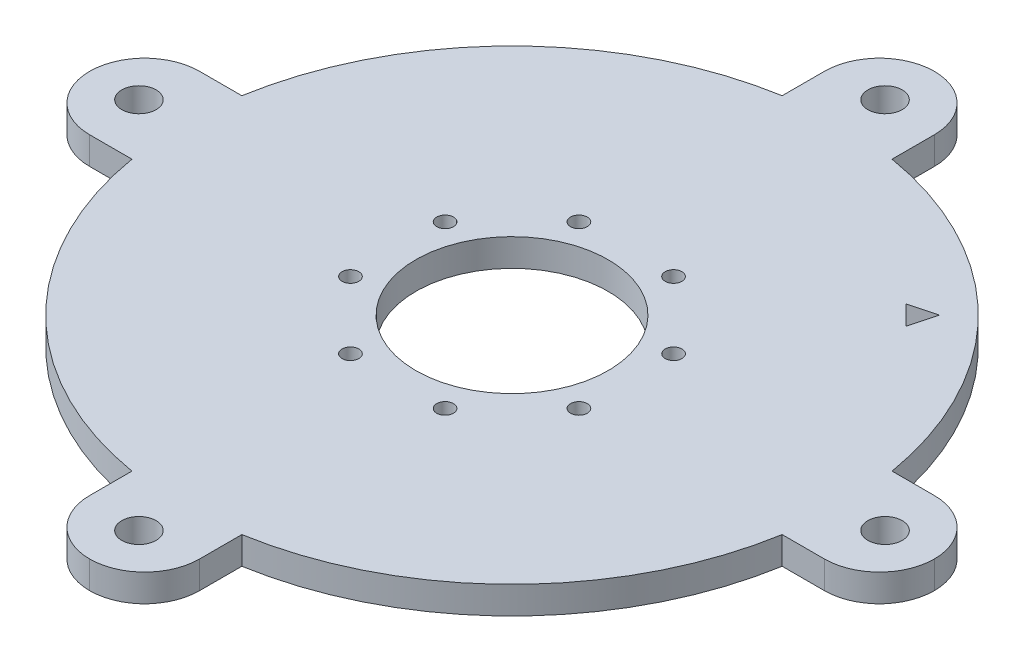
SolidWorks part; units mm, degrees
ref_plane "Front Plane" through (0, 0, 0) normal (0, 0, 1) x (1, 0, 0)
ref_plane "Top Plane" through (0, 0, 0) normal (0, 1, 0) x (1, 0, 0)
ref_plane "Right Plane" through (0, 0, 0) normal (1, 0, 0) x (0, 0, -1)
sketch "Sketch1" plane through (0, 0, 0) normal (0, 1, 0) x (1, 0, 0)
  circle A0 centre (0, 0) radius 155
  dimension "D1" = 310
extrude "Boss-Extrude1" add sketch "Sketch1" along normal blind 10
sketch "Sketch2" plane through (0, 10, 0) normal (0, 1, 0) x (1, 0, 0)
  line L0 (0, 135.7645) -> (135.7645, 0) construction
  line L1 (135.7645, 0) -> (0, -135.7645) construction
  line L2 (0, -135.7645) -> (-135.7645, 0) construction
  line L3 (-135.7645, 0) -> (0, 135.7645) construction
  line L4 (0, 0) -> (67.8823, 67.8823) construction
  line L5 (0, 0) -> (0, 55.7409) construction
  circle A0 centre (-135.7645, 0) radius 6.25
  circle A1 centre (0, -135.7645) radius 6.25
  circle A2 centre (135.7645, 0) radius 6.25
  circle A4 centre (0, 135.7645) radius 6.25
  dimension "D13" = 12.5
  dimension "D15" = 192
  dimension "D17" = 96
  dimension "D14" = 96
  dimension "D16" = 192
  dimension "D18" = 45
extrude "Cut-Extrude1" cut sketch "Sketch2" against normal through all
sketch "Sketch3" plane through (0, 10, 0) normal (0, 1, 0) x (1, 0, 0)
  circle A0 centre (0, 0) radius 35
  dimension "D1" = 70
extrude "Cut-Extrude2" cut sketch "Sketch3" against normal through all
sketch "Sketch4" plane through (0, 10, 0) normal (0, 1, 0) x (1, 0, 0)
  line L0 (0, 0) -> (0, 155) construction
  line L1 (0, 0) -> (59.3159, 143.2013) construction
  circle A0 centre (17.2208, 41.5746) radius 3.05
  circle A3 centre (0, 0) radius 155 construction
  dimension "D2" = 6.1
  dimension "D1" = 22.5
  dimension "D3" = 45
extrude "Cut-Extrude3" cut sketch "Sketch4" against normal through all
pattern_circular "CirPattern1" count 8 every 45 about axis through (0, 0, 0) along (0, 1, 0) of "Cut-Extrude3"
sketch "Sketch5" plane through (0, 10, 0) normal (0, 1, 0) x (1, 0, 0)
  line L0 (0, 0) -> (-155, 0) construction
  line L1 (0, 0) -> (0, 155) construction
  line L2 (-86.2957, 20) -> (-153.7043, 20)
  line L3 (-86.2957, 20) -> (-86.2957, -20)
  line L4 (-86.2957, -20) -> (-153.7043, -20)
  line L5 (-153.7043, 20) -> (-153.7043, -20)
  line L6 (-86.2957, 20) -> (-153.7043, -20) construction
  line L7 (-86.2957, -20) -> (-153.7043, 20) construction
  line L9 (-20, 86.2957) -> (20, 86.2957)
  line L10 (-20, 86.2957) -> (-20, 153.7043)
  line L11 (-20, 153.7043) -> (20, 153.7043)
  line L12 (20, 86.2957) -> (20, 153.7043)
  line L13 (-20, 86.2957) -> (20, 153.7043) construction
  line L14 (-20, 153.7043) -> (20, 86.2957) construction
  circle A0 centre (0, 0) radius 120
  circle A1 centre (0, 0) radius 155 construction
  point P3 (-120, 0)
  point P12 (0, 120)
  circle M30 centre (0, 0) radius 155
  dimension "D1" = 240
  dimension "D2" = 40
  dimension "D3" = 40
extrude "Cut-Extrude4" cut sketch "Sketch5" against normal blind 10 contours A0 L10 L2 M30 | L5 M30 region at (-91.3175, 10, -91.3175) region at (-154.2227, 10, 0)
pattern_circular "CirPattern3" count 4 every 90 about axis through (0, 0, 0) along (0, 1, 0) of "Cut-Extrude4"
fillet "Fillet1" radius 20 8 edges at (-153.7043, 5, -20) (-20, 5, 153.7043) (153.7043, 5, 20) (20, 5, -153.7043) (-153.7043, 5, 20) (20, 5, 153.7043) (153.7043, 5, -20) (-20, 5, -153.7043)
sketch "Sketch6" plane through (0, 10, 0) normal (0, 1, 0) x (1, 0, 0)
  line L0 (0, 0) -> (84.8528, 84.8528) construction
  line L2 (77.7817, 77.7817) -> (68.1225, 75.1936)
  line L3 (68.1225, 75.1936) -> (75.1936, 68.1225)
  line L4 (75.1936, 68.1225) -> (77.7817, 77.7817)
  arc A0 (118.3216, 20) -> (20, 118.3216) centre (0, 0) ccw construction
  circle A1 centre (73.6993, 73.6993) radius 2.8868 construction
  dimension "D1" = 10
  dimension "D2" = 10
extrude "Cut-Extrude5" cut sketch "Sketch6" against normal through all
equation "\"D14@Sketch2\"=\"D17@Sketch2\""
equation "\"D15@Sketch2\"=\"D16@Sketch2\""
equation "\"D3@Sketch5\" = \"D2@Sketch5\""
